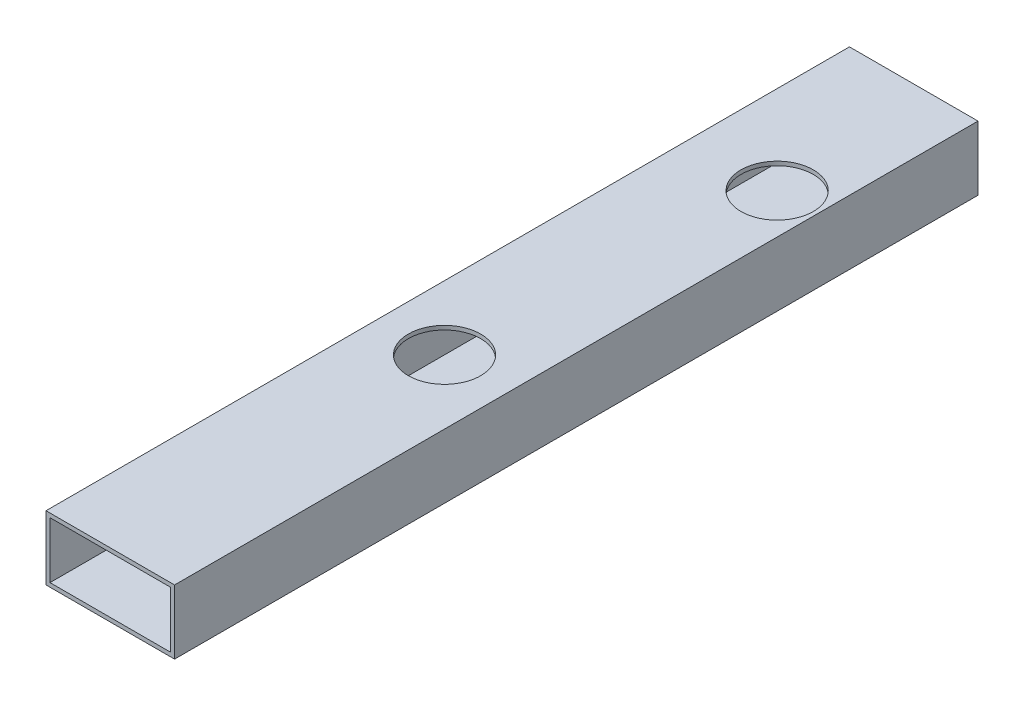
SolidWorks part; units mm, degrees
ref_plane "Front Plane" through (0, 0, 0) normal (0, 0, 1) x (1, 0, 0)
ref_plane "Top Plane" through (0, 0, 0) normal (0, 1, 0) x (1, 0, 0)
ref_plane "Right Plane" through (0, 0, 0) normal (1, 0, 0) x (0, 0, -1)
sketch "Sketch1" plane through (0, 0, 0) normal (0, 0, 1) x (1, 0, 0)
  line L0 (-23.8125, 11.1125) -> (23.8125, 11.1125)
  line L2 (-25.4, 12.7) -> (25.4, 12.7)
  line L3 (-25.4, 12.7) -> (-25.4, -12.7)
  line L4 (-25.4, -12.7) -> (25.4, -12.7)
  line L5 (25.4, 12.7) -> (25.4, -12.7)
  line L10 (23.8125, 11.1125) -> (23.8125, -11.1125)
  line L11 (-23.8125, -11.1125) -> (23.8125, -11.1125)
  line L12 (-23.8125, 11.1125) -> (-23.8125, -11.1125)
  point P12 (0, 12.7)
  point P14 (25.4, 0)
  dimension "Wall Thickness" = 1.5875
  dimension "Outside Width" = 50.8
  dimension "Outside Height" = 25.4
  dimension "Inside Height" = 22.225
  dimension "Inside Width" = 47.625
sketch "Sketch2" plane through (0, 0, 0) normal (1, 0, 0) x (0, 0, -1)
  line L0 (158.75, 0) -> (-158.75, 0)
  point P4 (0, 0)
  point P7 (-158.75, 0)
  point P10 (158.75, 0)
  dimension "Length" = 317.5
sketch "Sketch3" plane through (0, 0, 0) normal (0, 0, 1) x (1, 0, 0)
  line L21 (25.4, 12.7) -> (-25.4, 12.7)
  line L22 (25.4, -12.7) -> (25.4, 12.7)
  line L23 (-25.4, -12.7) -> (25.4, -12.7)
  line L24 (-25.4, 12.7) -> (-25.4, -12.7)
  line L25 (25.4, 12.7) -> (-25.4, 12.7)
  line L26 (25.4, -12.7) -> (25.4, 12.7)
  line L27 (-25.4, -12.7) -> (25.4, -12.7)
  line L28 (-25.4, 12.7) -> (-25.4, -12.7)
  line L29 (23.8125, 11.1125) -> (-23.8125, 11.1125)
  line L30 (23.8125, -11.1125) -> (23.8125, 11.1125)
  line L31 (-23.8125, -11.1125) -> (23.8125, -11.1125)
  line L32 (-23.8125, 11.1125) -> (-23.8125, -11.1125)
  line L33 (23.8125, 11.1125) -> (-23.8125, 11.1125)
  line L34 (23.8125, -11.1125) -> (23.8125, 11.1125)
  line L35 (-23.8125, -11.1125) -> (23.8125, -11.1125)
  line L36 (-23.8125, 11.1125) -> (-23.8125, -11.1125)
  dimension "D1" = 0
  dimension "D2" = 0
extrude "Boss-Extrude1" add sketch "Sketch3" along normal up to vertex (158.75 mm away) and the other way up to vertex (158.75 mm away) up to point (0, 0, 158.75) other way up to point (0, 0, -158.75)
sketch "Drawing Reference" plane through (0, 0, 0) normal (1, 0, 0) x (0, 0, -1)
  line L0 (-158.75, 0) -> (158.75, 0) construction
  line L1 (0, -12.7) -> (0, 12.7) construction
  line L2 (-158.75, -12.7) -> (158.75, -12.7) construction
  line L5 (-158.75, 12.7) -> (158.75, 12.7) construction
  point P7 (-122.174, 0)
  point P8 (122.174, 0)
  dimension "D1" = 36.576
sketch "Sketch4" plane through (0, 12.7, 0) normal (0, 1, 0) x (1, 0, 0)
  line L0 (0, 158.75) -> (0, 95.25) construction
  line L1 (25.4, 158.75) -> (-25.4, 158.75) construction
  line L2 (0, 95.25) -> (9.525, 95.25) construction
  line L3 (0, 158.75) -> (0, -26.67) construction
  circle A1 centre (9.525, 95.25) radius 14.2875
  circle A2 centre (0, -26.67) radius 14.2875
  dimension "D1" = 63.5
  dimension "D2" = 9.525
extrude "Cut-Extrude1" cut sketch "Sketch4" against normal blind 39.37
equation "\"D1@Drawing Reference\"=\"Outside Width@Sketch1\" * 0.72"
